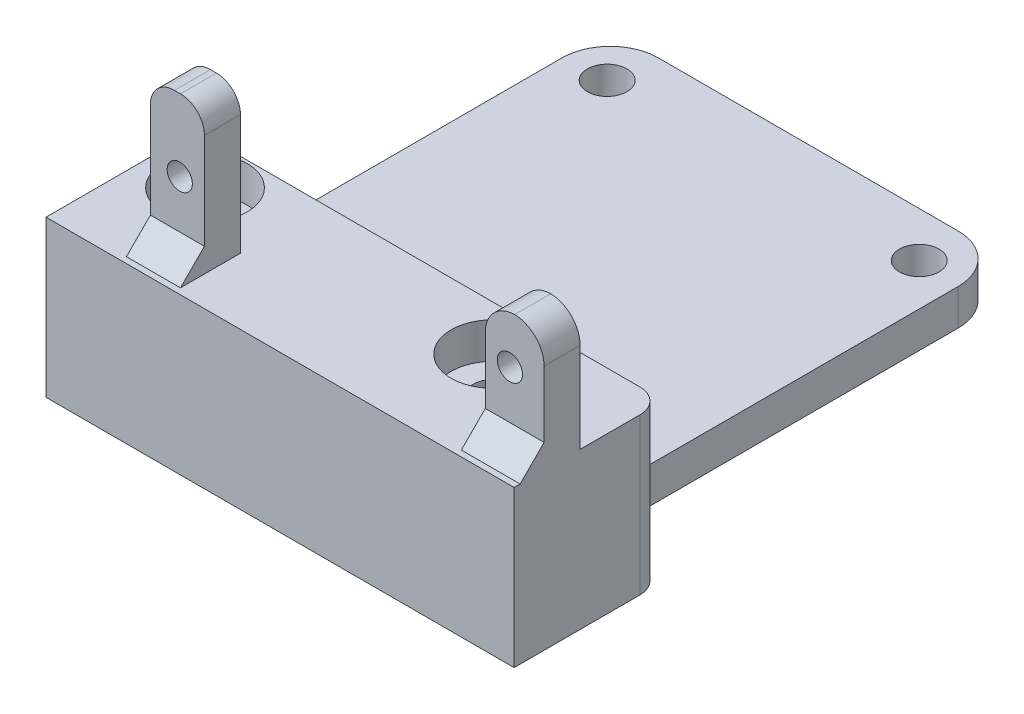
SolidWorks part; units mm, degrees
ref_plane "Front Plane" through (0, 0, 0) normal (0, 0, 1) x (1, 0, 0)
ref_plane "Top Plane" through (0, 0, 0) normal (0, 1, 0) x (1, 0, 0)
ref_plane "Right Plane" through (0, 0, 0) normal (1, 0, 0) x (0, 0, -1)
sketch "Sketch1" plane through (0, 0, 0) normal (0, 1, 0) x (1, 0, 0)
  line L1 (0, 0) -> (33, 0)
  line L2 (0, 0) -> (0, 42)
  line L3 (0, 42) -> (33, 42)
  line L4 (33, 0) -> (33, 42)
  dimension "D1" = 42
  dimension "D2" = 33
extrude "Boss-Extrude1" add sketch "Sketch1" along normal blind 5
ref_plane "Plane1" through (23, 0, -42) normal (1, 0, 0) x (0, 0, -1)
sketch "Sketch4" plane through (0, 5, 0) normal (0, 1, 0) x (1, 0, 0)
  circle A0 centre (4.5, 3.75) radius 1.65 construction
  circle A1 centre (3.5, 38.25) radius 1.65 construction
  circle A2 centre (29.5, 38.25) radius 1.65 construction
  circle A3 centre (28.5, 3.75) radius 1.65 construction
  circle A4 centre (4.5, 3.75) radius 1.65
  circle A5 centre (3.5, 38.25) radius 1.65
  circle A6 centre (29.5, 38.25) radius 1.65
  circle A7 centre (28.5, 3.75) radius 1.65
extrude "Cut-Extrude1" cut sketch "Sketch4" against normal blind 10
sketch "Sketch6" plane through (0, 5, 0) normal (0, 1, 0) x (1, 0, 0)
  line L0 (33, 0) -> (33, 42) construction
  line L1 (33, 0) -> (39, 0)
  line L2 (33, 0) -> (33, 7.4907)
  line L3 (33, 7.4907) -> (39, 7.4907)
  line L4 (39, 0) -> (39, 7.4907)
  line L5 (39, -5) -> (0, -5)
  line L6 (39, -5) -> (39, 0)
  line L7 (39, 0) -> (0, 0)
  line L8 (0, -5) -> (0, 0)
  line M11 (0, 0) -> (33, 0)
  line M12 (33, 0) -> (33, 42)
  dimension "D1" = 5
  dimension "D2" = 6
extrude "Boss-Extrude2" add sketch "Sketch6" against normal blind 5 contours L1 L4 L3 M12 | L8 L5 L6 L1 M11 region at (36, 5, -3.7453) region at (19.5, 5, 2.5)
sketch "Sketch8" plane through (0, 5, 0) normal (0, 1, 0) x (1, 0, 0)
  line L6 (39, 7.4907) -> (33, 7.4907)
  line L7 (33, 7.4907) -> (33, 42)
  line L8 (33, 42) -> (0, 42)
  line L9 (0, 42) -> (0, -5)
  line L10 (0, -5) -> (39, -5)
  line L11 (39, -5) -> (39, 7.4907)
  line L12 (39, 7.4907) -> (33, 7.4907)
  line L13 (33, 7.4907) -> (33, 42)
  line L14 (33, 42) -> (0, 42)
  line L15 (0, 42) -> (0, -5)
  line L16 (0, -5) -> (39, -5)
  line L17 (39, -5) -> (39, 7.4907)
  circle A0 centre (29.5, 38.25) radius 1.65 construction
  circle A1 centre (3.5, 38.25) radius 1.65 construction
  circle A2 centre (4.5, 3.75) radius 1.65 construction
  circle A3 centre (28.5, 3.75) radius 1.65 construction
  circle A4 centre (29.5, 38.25) radius 1.65
  circle A5 centre (3.5, 38.25) radius 1.65
  circle A6 centre (4.5, 3.75) radius 1.65
  circle A7 centre (28.5, 3.75) radius 1.65
  dimension "D1" = 0
extrude "Boss-Extrude4" add sketch "Sketch8" along normal blind 10
sketch "Sketch9" plane through (0, 15, 0) normal (0, 1, 0) x (1, 0, 0)
  line L0 (39, -5) -> (39, 7.4907) construction
  line L1 (39, 0.5) -> (34.1, 0.5)
  line L2 (39, 0.5) -> (39, -2.5)
  line L3 (39, -2.5) -> (34.1, -2.5)
  line L4 (34.1, 0.5) -> (34.1, -2.5)
  line L5 (0, -5) -> (39, -5) construction
  dimension "D1" = 3
  dimension "D2" = 2.5
  dimension "D3" = 4.9
extrude "Boss-Extrude5" add sketch "Sketch9" along normal blind 10
fillet "Fillet2" radius 2.5 2 edges at (34.1, 25, 1) (39, 25, 1)
sketch "Sketch10" plane through (0, 0, -0.5) normal (0, 0, -1) x (-1, 0, 0)
  arc A0 (-37.0682, 20.5) -> (-37.0682, 21.5) centre (-36.1449, 21) ccw construction
  arc A1 (-37.0682, 20.5) -> (-37.0682, 21.5) centre (-36.1449, 21) ccw
  circle A2 centre (-36.1449, 21) radius 1.05
extrude "Cut-Extrude3" cut sketch "Sketch10" against normal blind 10 contours A1 A2 region at (36.1449, 21, -0.5)
sketch "Sketch11" plane through (0, 15, 0) normal (0, 1, 0) x (1, 0, 0)
  line L1 (0, 42) -> (33, 42)
  line L2 (0, 42) -> (0, 7.4907)
  line L3 (0, 7.4907) -> (33, 7.4907)
  line L4 (33, 42) -> (33, 7.4907)
extrude "Cut-Extrude4" cut sketch "Sketch11" against normal blind 10
fillet "Fillet3" radius 4 3 edges at (33, 2.5, -7.4907) (0, 2.5, -42) (33, 2.5, -42)
fillet "Fillet4" radius 2 1 edges at (39, 7.5, -7.4907)
fillet "Fillet5" radius 4 1 edges at (18.5, 5, -7.4907)
sketch "Sketch12" plane through (0, 15, 0) normal (0, 1, 0) x (1, 0, 0)
  circle A0 centre (4.5, 3.75) radius 3.5
  circle A1 centre (28.5, 3.75) radius 3.5
  dimension "D1" = 7
  dimension "D2" = 7
extrude "Cut-Extrude5" cut sketch "Sketch12" against normal blind 3
sketch "Sketch13" plane through (0, 15, 0) normal (0, 1, 0) x (1, 0, 0)
  line L0 (0, 7.4907) -> (0, -5) construction
  line L1 (10.7, 0.5) -> (6.2, 0.5)
  line L2 (10.7, 0.5) -> (10.7, -2.5)
  line L3 (10.7, -2.5) -> (6.2, -2.5)
  line L4 (6.2, 0.5) -> (6.2, -2.5)
  line L5 (6.3699, 0.5) -> (11.1449, 0.5) construction
  dimension "D1" = 4.5
  dimension "D2" = 6.2
  dimension "D3" = 3
  dimension "D4" = 0
extrude "Boss-Extrude6" add sketch "Sketch13" along normal up to surface (12 mm away)
fillet "Fillet6" radius 2 2 edges at (6.2, 27, 1) (10.7, 27, 1)
sketch "Sketch14" plane through (0, 0, -0.5) normal (0, 0, -1) x (-1, 0, 0)
  arc A0 (-7.7216, 21.5) -> (-7.7216, 20.5) centre (-8.6449, 21) ccw construction
  arc A1 (-7.7216, 21.5) -> (-7.7216, 20.5) centre (-8.6449, 21) ccw
  circle A2 centre (-8.6449, 21) radius 1.05
extrude "Cut-Extrude6" cut sketch "Sketch14" against normal blind 7 contours A1 A2 region at (8.6449, 21, -0.5)
chamfer "Chamfer1" distance 2 angle 45 2 edges at (36.55, 15, 2.5) (8.45, 15, 2.5)
sketch "Sketch15" plane through (0, 0, 0) normal (0, -1, 0) x (1, 0, 0)
  line L5 (39, -5.4907) -> (39, 5)
  line L6 (39, 5) -> (0, 5)
  line L7 (0, 5) -> (0, -38)
  line L8 (4, -42) -> (29, -42)
  line L9 (33, -38) -> (33, -11.4907)
  line L10 (39, -5.4907) -> (39, 5)
  line L11 (39, 5) -> (0, 5)
  line L12 (0, 5) -> (0, -38)
  line L13 (4, -42) -> (29, -42)
  line L14 (33, -38) -> (33, -11.4907)
  arc A4 (37, -7.4907) -> (33, -11.4907) centre (37, -11.4907) ccw
  arc A5 (37, -7.4907) -> (39, -5.4907) centre (37, -5.4907) ccw
  arc A6 (0, -38) -> (4, -42) centre (4, -38) ccw
  arc A7 (29, -42) -> (33, -38) centre (29, -38) ccw
  arc A8 (37, -7.4907) -> (33, -11.4907) centre (37, -11.4907) ccw
  arc A9 (37, -7.4907) -> (39, -5.4907) centre (37, -5.4907) ccw
  arc A10 (0, -38) -> (4, -42) centre (4, -38) ccw
  arc A11 (29, -42) -> (33, -38) centre (29, -38) ccw
  dimension "D1" = 0
extrude "Cut-Extrude7" cut sketch "Sketch15" against normal blind 2
